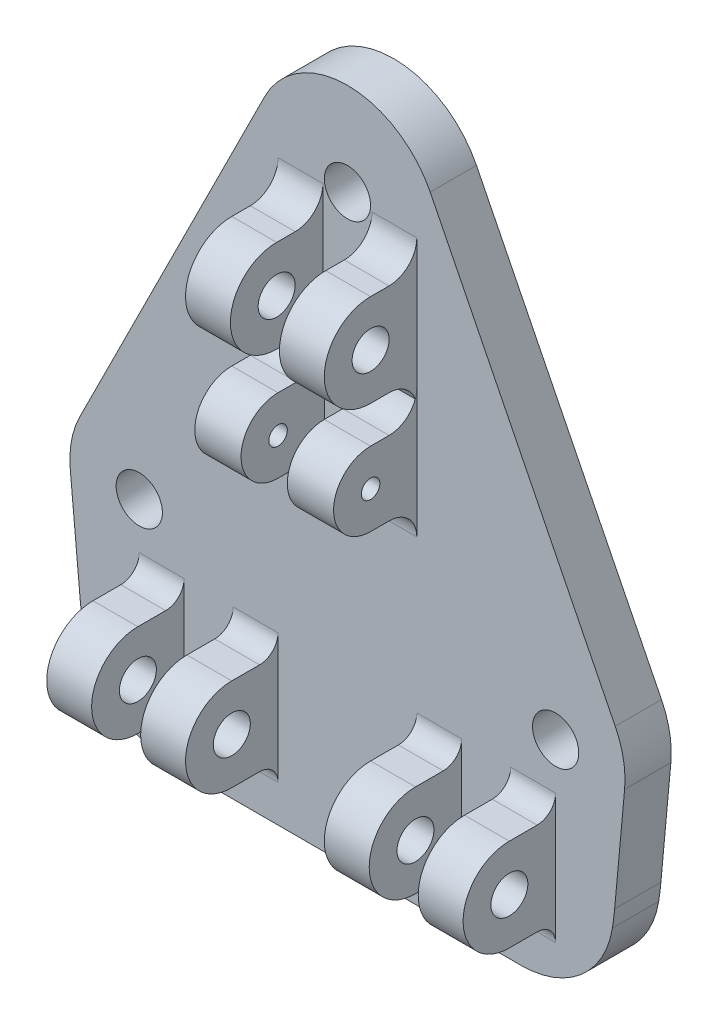
SolidWorks part; units mm, degrees
other "Markup1"
sketch "Sketch9" plane through (30, 50, 15) normal (0.9984, 0.0211, 0.0518) x (0.0521, -0.0136, -0.9985)
material "ABS"
ref_plane "Front Plane" through (0, 0, 0) normal (0, 0, 1) x (1, 0, 0)
ref_plane "Top Plane" through (0, 0, 0) normal (0, 1, 0) x (1, 0, 0)
ref_plane "Right Plane" through (0, 0, 0) normal (1, 0, 0) x (0, 0, -1)
sketch "Sketch1" plane through (0, 0, 0) normal (0, 0, 1) x (1, 0, 0)
  line L0 (28.9443, 4.4721) -> (8.9443, 44.4721)
  line L1 (-8.9443, 44.4721) -> (-28.9443, 4.4721)
  line L2 (-29.958, -0.9159) -> (-28.8781, -12.6562)
  line L3 (28.8781, -12.6562) -> (29.958, -0.9159)
  arc A0 (8.9443, 44.4721) -> (-8.9443, 44.4721) centre (0, 40) ccw
  arc A1 (-28.8781, -12.6562) -> (28.8781, -12.6562) centre (0, -10) ccw
  arc A2 (28.9443, 4.4721) -> (29.958, -0.9159) centre (20, 0) cw
  arc A3 (-28.9443, 4.4721) -> (-29.958, -0.9159) centre (-20, 0) ccw
  dimension "D1" = 10
  dimension "D2" = 10
  dimension "D3" = 29
  dimension "D4" = 50
  dimension "D5" = 40
  dimension "D6" = 40
extrude "Boss-Extrude1" add sketch "Sketch1" along normal blind 5
sketch "Sketch2" plane through (0, 0, 5) normal (0, 0, 1) x (1, 0, 0)
  circle A0 centre (0, 40) radius 2.5
  circle A2 centre (22.5, 0) radius 2.5
  circle A3 centre (-22.5, 0) radius 2.5
  dimension "D1" = 5
  dimension "D2" = 45
  dimension "D3" = 22.5
  dimension "D5" = 40
extrude "Cut-Extrude1" cut sketch "Sketch2" against normal through all
sketch "Sketch3" plane through (0, 0, 0) normal (1, 0, 0) x (0, 0, -1)
  line L0 (-5, 22.4721) -> (-5, 14.4721)
  line L1 (-5, 4.4721) -> (-5, 44.4721) construction
  line L2 (-5, 14.4721) -> (-10, 14.4721)
  line L3 (-10, 22.4721) -> (-5, 22.4721)
  line L9 (-5, 44.4721) -> (0, 44.4721) construction
  arc A0 (-10, 14.4721) -> (-10, 22.4721) centre (-10, 18.4721) cw
  circle A3 centre (-10, 18.4721) radius 1
  dimension "D5" = 4
  dimension "D6" = 2
  dimension "D7" = 5
  dimension "D8" = 22
extrude "Boss-Extrude2" add sketch "Sketch3" along normal mid plane 15
sketch "Sketch5" plane through (0, 22.4721, 0) normal (0, 1, 0) x (1, 0, 0)
  line L0 (-7.5, -14) -> (7.5, -14) construction
  line L1 (-2.5, -23) -> (2.5, -23)
  line L2 (-2.5, -23) -> (-2.5, -5)
  line L3 (-2.5, -5) -> (2.5, -5)
  line L4 (2.5, -23) -> (2.5, -5)
  line L5 (-2.5, -23) -> (2.5, -5) construction
  line L6 (-2.5, -5) -> (2.5, -23) construction
  line L7 (-8.9443, -5) -> (8.9443, -5) construction
  point P0 (0, -14)
  dimension "D1" = 5
extrude "Cut-Extrude3" cut sketch "Sketch5" against normal up to surface (8 mm away) up to face at (0, 14.4721, 7.5)
fillet "Fillet1" radius 3 4 edges at (5, 14.4721, 5) (-5, 14.4721, 5) (5, 22.4721, 5) (-5, 22.4721, 5)
sketch "Sketch6" plane through (0, 0, 0) normal (1, 0, 0) x (0, 0, -1)
  line L0 (-5, 26.4721) -> (-5, 36.4721)
  line L1 (-5, 4.4721) -> (-5, 44.4721) construction
  line L2 (-5, 36.4721) -> (-10, 36.4721)
  line L3 (-10, 26.4721) -> (-5, 26.4721)
  line L4 (-5, 44.4721) -> (0, 44.4721) construction
  arc A0 (-10, 36.4721) -> (-10, 26.4721) centre (-10, 31.4721) ccw
  circle A1 centre (-10, 31.4721) radius 2
  dimension "D1" = 4
  dimension "D2" = 5
  dimension "D3" = 5
  dimension "D4" = 8
extrude "Boss-Extrude3" add sketch "Sketch6" along normal mid plane 15
sketch "Sketch7" plane through (0, 36.4721, 0) normal (0, 1, 0) x (1, 0, 0)
  line L0 (-7.5, -15) -> (7.5, -15) construction
  line L1 (-2.65, -25) -> (2.65, -25)
  line L2 (-2.65, -25) -> (-2.65, -5)
  line L3 (-2.65, -5) -> (2.65, -5)
  line L4 (2.65, -25) -> (2.65, -5)
  line L5 (-2.65, -25) -> (2.65, -5) construction
  line L6 (-2.65, -5) -> (2.65, -25) construction
  line L7 (7.5, -5) -> (-7.5, -5) construction
  point P0 (0, -15)
  dimension "D1" = 5.3
extrude "Cut-Extrude4" cut sketch "Sketch7" against normal up to surface (10 mm away) up to face at (0, 26.4721, 7.5)
fillet "Fillet2" radius 3 4 edges at (-5.075, 36.4721, 5) (5.075, 36.4721, 5) (-5.075, 26.4721, 5) (5.075, 26.4721, 5)
sketch "Sketch8" plane through (0, 0, 5) normal (0, 0, 1) x (1, 0, 0)
  line L0 (-25.923, -23) -> (25.923, -23)
  line L4 (28.8781, -12.6562) -> (29.958, -0.9159)
  line L5 (28.9443, 4.4721) -> (8.9443, 44.4721)
  line L6 (-8.9443, 44.4721) -> (-28.9443, 4.4721)
  line L7 (-29.958, -0.9159) -> (-28.8781, -12.6562)
  arc A4 (-28.8781, -12.6562) -> (28.8781, -12.6562) centre (0, -10) ccw
  arc A5 (29.958, -0.9159) -> (28.9443, 4.4721) centre (20, 0) ccw
  arc A6 (8.9443, 44.4721) -> (-8.9443, 44.4721) centre (0, 40) ccw
  arc A7 (-28.9443, 4.4721) -> (-29.958, -0.9159) centre (-20, 0) ccw
  arc A8 (-25.923, -23) -> (25.923, -23) centre (0, -10) ccw
  dimension "D2" = 16
  dimension "D1" = 0
extrude "Cut-Extrude5" cut sketch "Sketch8" against normal through all
fillet "Fillet4" radius 10 2 edges at (25.923, -23, 2.5) (-25.923, -23, 2.5)
sketch "Sketch10" plane through (0, 0, 0) normal (1, 0, 0) x (0, 0, -1)
  line L0 (-5, -17) -> (-10, -17)
  line L2 (-10, -7) -> (-5, -7)
  line L3 (-5, -12.6562) -> (-5, -0.9159) construction
  line L4 (-5, -7) -> (-5, -17)
  line L6 (0, -23) -> (-5, -23) construction
  arc A0 (-10, -17) -> (-10, -7) centre (-10, -12) cw
  circle A1 centre (-10, -12) radius 2
  dimension "D1" = 4
  dimension "D2" = 5
  dimension "D3" = 5
  dimension "D4" = 6
extrude "Boss-Extrude4" add sketch "Sketch10" along normal mid plane 45
sketch "Sketch11" plane through (0, -17, 0) normal (0, -1, 0) x (1, 0, 0)
  line L0 (22.5, 15) -> (-22.5, 15) construction
  line L1 (-7.5, 25) -> (7.5, 25)
  line L2 (-7.5, 25) -> (-7.5, 5)
  line L3 (-7.5, 5) -> (7.5, 5)
  line L4 (7.5, 25) -> (7.5, 5)
  line L5 (-7.5, 25) -> (7.5, 5) construction
  line L6 (-7.5, 5) -> (7.5, 25) construction
  line L7 (18.7617, 5) -> (-18.7617, 5) construction
  line L9 (-17.65, 25) -> (-12.35, 25)
  line L10 (-17.65, 25) -> (-17.65, 5)
  line L11 (-17.65, 5) -> (-12.35, 5)
  line L12 (-12.35, 25) -> (-12.35, 5)
  line L13 (-17.65, 25) -> (-12.35, 5) construction
  line L14 (-17.65, 5) -> (-12.35, 25) construction
  point P0 (0, 15)
  point P9 (-15, 15)
  point P14 (10.6957, 15)
  dimension "D1" = 15
  dimension "D2" = 5.3
  dimension "D3" = 15
extrude "Cut-Extrude6" cut sketch "Sketch11" against normal up to surface (10 mm away) up to face at (0, -7, 7.5)
mirror "Mirror1" about plane through (0, 0, 0) normal (1, 0, 0) of "Cut-Extrude6"
fillet "Fillet5" radius 2 8 edges at (20.075, -17, 5) (-20.075, -17, 5) (-20.075, -7, 5) (-9.925, -7, 5) (9.925, -7, 5) (20.075, -7, 5) (9.925, -17, 5) (-9.925, -17, 5)
